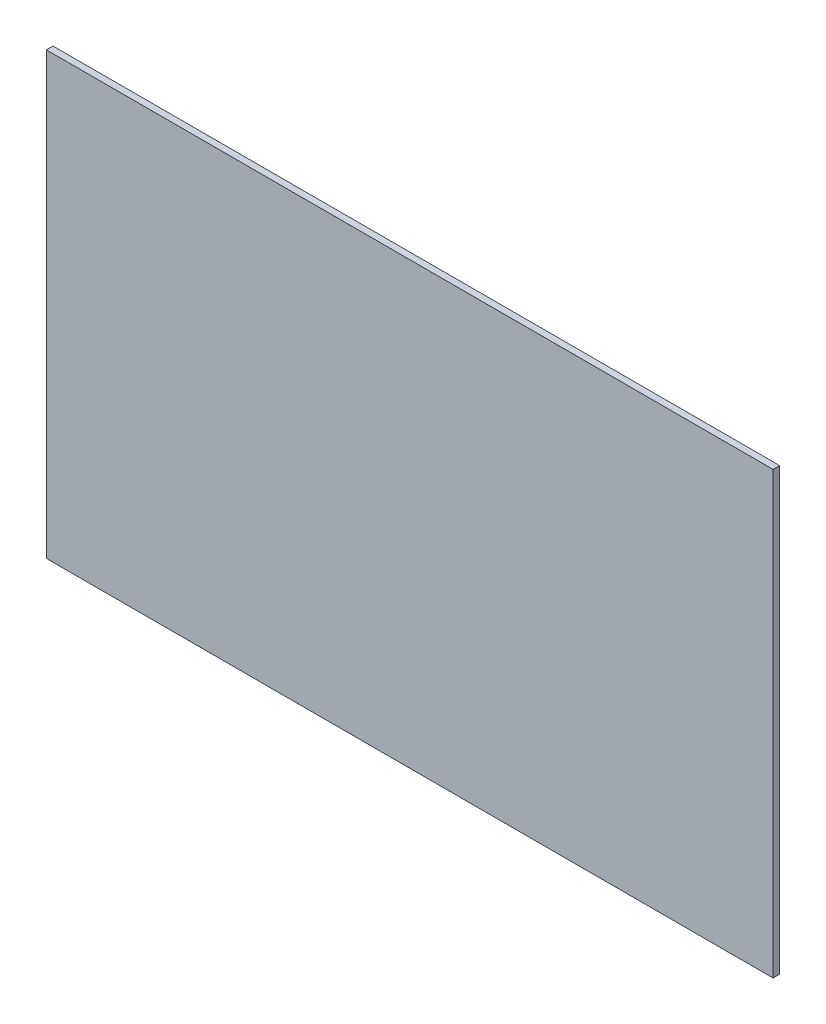
SolidWorks part; units mm, degrees
ref_plane "Alzado" through (0, 0, 0) normal (0, 0, 1) x (1, 0, 0)
ref_plane "Planta" through (0, 0, 0) normal (0, 1, 0) x (1, 0, 0)
ref_plane "Vista lateral" through (0, 0, 0) normal (1, 0, 0) x (0, 0, -1)
sketch "Croquis1" plane through (0, 0, 0) normal (0, 0, 1) x (1, 0, 0)
  line L1 (-165, 100) -> (165, 100)
  line L2 (-165, 100) -> (-165, -100)
  line L3 (-165, -100) -> (165, -100)
  line L4 (165, 100) -> (165, -100)
  line L5 (-165, 100) -> (165, -100) construction
  line L6 (-165, -100) -> (165, 100) construction
  point P0 (0, 0)
  dimension "D1" = 330
  dimension "D2" = 200
extrude "Saliente-Extruir1" add sketch "Croquis1" along normal blind 3
equation "\"largo\"= 330mm"
equation "\"ancho\"= 200mm"
